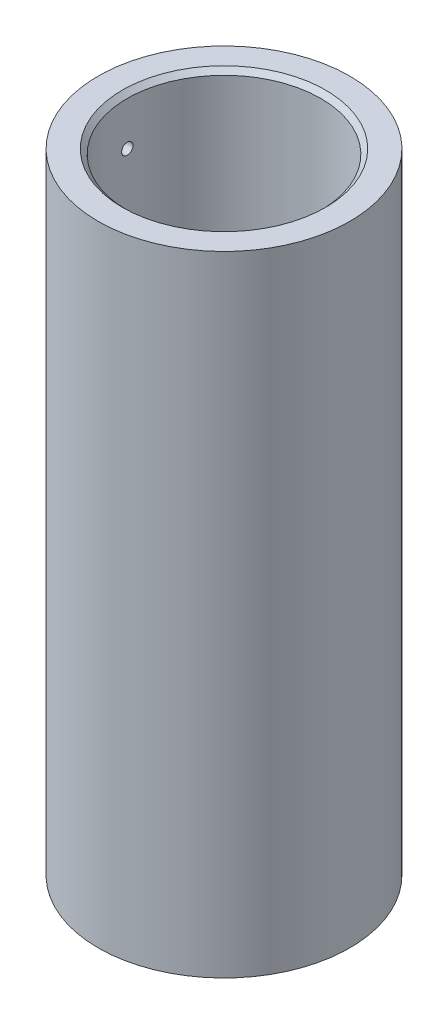
SolidWorks part; units mm, degrees
ref_plane "Front Plane" through (0, 0, 0) normal (0, 0, 1) x (1, 0, 0)
ref_plane "Top Plane" through (0, 0, 0) normal (0, 1, 0) x (1, 0, 0)
ref_plane "Right Plane" through (0, 0, 0) normal (1, 0, 0) x (0, 0, -1)
sketch "Sketch1" plane through (0, 0, 0) normal (0, 1, 0) x (1, 0, 0)
  circle A0 centre (0, 0) radius 10
  circle A1 centre (0, 0) radius 13
  dimension "D1" = 20
  dimension "D2" = 26
extrude "Boss-Extrude1" add sketch "Sketch1" along normal blind 65
chamfer "Chamfer1" distance 0.5 angle 45 2 edges at (0, 0, 10) (0, 65, 10)
sketch "Sketch5" plane through (0, 0, 0) normal (0, 0, 1) x (1, 0, 0)
  line L0 (13, 65) -> (-13, 65) construction
  line L1 (-13, 60.585) -> (-9, 60.585) construction
  line L2 (-13, 60.585) -> (-13, 59.415) construction
  line L3 (-13, 59.415) -> (-9, 59.415) construction
  line L4 (-9, 60.585) -> (-9, 59.415) construction
  line L5 (-13, 60.585) -> (-9, 59.415) construction
  line L6 (-13, 59.415) -> (-9, 60.585) construction
  line L8 (-13, 60.949) -> (-12, 60.585)
  line L9 (-12, 60.585) -> (-9, 60.585)
  line L10 (-9, 60.585) -> (-9, 60)
  line L13 (-13, 65) -> (-13, 0) construction
  line L14 (-13, 60.949) -> (-13, 60)
  line L15 (-13, 60) -> (-9, 60)
  point P0 (-11, 60)
  dimension "D1" = 1.17
  dimension "D2" = 5
  dimension "D4" = 20
  dimension "D3" = 4
  dimension "D5" = 1
revolve "Cut-Revolve4" cut sketch "Sketch5" angle 360 about L15
equation "\"pin_bore\"=10.20"
equation "\"top_outer_diameter\"=16.00"
equation "\"bottom_height\"=16.50"
equation "\"bottom_bore_height\"=8.50"
equation "\"valve_diameter\"=1.17"
equation "\"D1@Sketch5\"=\"valve_diameter\""
